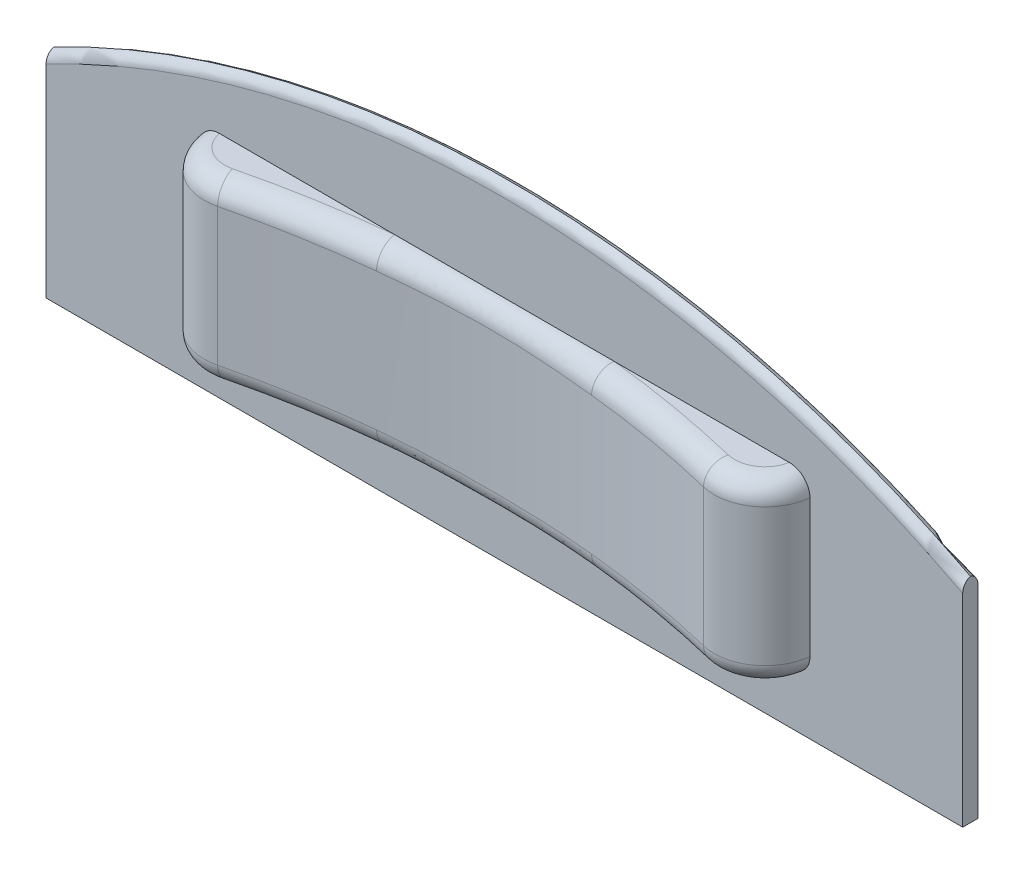
SolidWorks part; units mm, degrees
ref_plane "Front Plane" through (0, 0, 0) normal (0, 0, 1) x (1, 0, 0)
ref_plane "Top Plane" through (0, 0, 0) normal (0, 1, 0) x (1, 0, 0)
ref_plane "Right Plane" through (0, 0, 0) normal (1, 0, 0) x (0, 0, -1)
sketch "Sketch1" plane through (0, 0, 0) normal (0, 0, 1) x (1, 0, 0)
  line L0 (180, 0) -> (180, -42)
  line L1 (0, 0) -> (0, -42)
  line L2 (0, -42) -> (180, -42)
  arc A0 (0, 0) -> (180, 0) centre (90, -173.0909) cw
  point P3 (90, 22)
  dimension "D1" = 22
  dimension "D2" = 42
  dimension "D3" = 42
  dimension "D4" = 180
extrude "Boss-Extrude1" add sketch "Sketch1" along normal blind 3 contours L2 L0 A0 L1
sketch "Sketch2" plane through (0, 0, 3) normal (0, 0, 1) x (1, 0, 0)
  line L0 (0, -42) -> (180, -42) construction
  line L1 (30, 3) -> (150, 3)
  line L2 (30, 3) -> (30, -32)
  line L3 (30, -32) -> (150, -32)
  line L4 (150, 3) -> (150, -32)
  line L5 (180, 0) -> (180, -42) construction
  line L6 (0, 0) -> (0, -42) construction
  dimension "D1" = 10
  dimension "D2" = 30
  dimension "D3" = 30
  dimension "D4" = 35
extrude "Boss-Extrude2" add sketch "Sketch2" along normal blind 12
sketch "Sketch3" plane through (0, 3, 0) normal (0, 1, 0) x (1, 0, 0)
  line L0 (150, -15) -> (150, -3) construction
  line L1 (150, -15) -> (30, -15) construction
  line L2 (30, -15) -> (150, -15)
  arc A0 (30, -15) -> (150, -15) centre (90, -207.6038) cw
extrude "Cut-Extrude1" cut sketch "Sketch3" against normal up to next
fillet "Fillet1" radius 10 2 edges at (150, -14.5, 15) (30, -14.5, 15)
fillet "Fillet2" radius 4 6 edges at (145.7894, -32, 10.073) (90, -32, 5.8708) (34.2106, -32, 10.073) (145.7894, 3, 10.073) (90, 3, 5.8708) (34.2106, 3, 10.073)
fillet "Fillet3" radius 2 2 edges at (90, 22, 0) (90, 22, 3)
